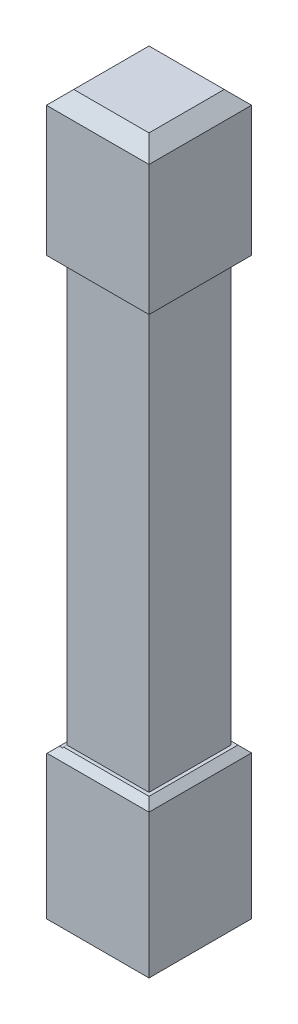
SolidWorks part; units mm, degrees
ref_plane "Plan de face" through (0, 0, 0) normal (0, 0, 1) x (1, 0, 0)
ref_plane "Plan de dessus" through (0, 0, 0) normal (0, 1, 0) x (1, 0, 0)
ref_plane "Plan de droite" through (0, 0, 0) normal (1, 0, 0) x (0, 0, -1)
sketch "Esquisse1" plane through (0, 0, 0) normal (0, 0, 1) x (1, 0, 0)
  line L0 (0, 658.8921) -> (0, -474.8551) construction
  line L2 (0, 685.5097) -> (-75, 685.5097)
  line L3 (0, 685.5097) -> (0, -364.4903)
  line L4 (0, -364.4903) -> (-75, -364.4903)
  line L5 (-75, 685.5097) -> (-75, -364.4903)
  dimension "D1" = 1050
  dimension "D2" = 75
extrude "Boss.-Extru.2" add sketch "Esquisse1" along normal blind 150
mirror "Symétrie1" about plane through (0, 685.5097, 150) normal (-1, 0, 0) of "Boss.-Extru.2"
sketch "Esquisse2" plane through (0, 0, 0) normal (0, 0, 1) x (1, 0, 0)
  line L0 (75, 685.5097) -> (-75, 685.5097) construction
  line L1 (-113.4667, 465.5097) -> (113.4667, 465.5097)
  line L2 (-113.4667, 465.5097) -> (-113.4667, -144.4903)
  line L3 (-113.4667, -144.4903) -> (113.4667, -144.4903)
  line L4 (113.4667, 465.5097) -> (113.4667, -144.4903)
  dimension "D1" = 610
  dimension "D2" = 220
extrude "Enlèv. mat.-Extru.1" cut sketch "Esquisse2" along normal blind 15
sketch "Esquisse3" plane through (-75, 0, 0) normal (-1, 0, 0) x (0, 0, 1)
  line L1 (0, 465.5097) -> (179.7824, 465.5097)
  line L2 (0, 465.5097) -> (0, -145.4548)
  line L3 (0, -145.4548) -> (179.7824, -145.4548)
  line L4 (179.7824, 465.5097) -> (179.7824, -145.4548)
extrude "Enlèv. mat.-Extru.2" cut sketch "Esquisse3" against normal blind 15
sketch "Esquisse4" plane through (75, 0, 0) normal (1, 0, 0) x (0, 0, -1)
  line L1 (0, 465.5097) -> (-199.3417, 465.5097)
  line L2 (0, 465.5097) -> (0, -144.4903)
  line L3 (0, -144.4903) -> (-199.3417, -144.4903)
  line L4 (-199.3417, 465.5097) -> (-199.3417, -144.4903)
extrude "Enlèv. mat.-Extru.3" cut sketch "Esquisse4" against normal blind 15
sketch "Esquisse5" plane through (0, 0, 150) normal (0, 0, 1) x (1, 0, 0)
  line L1 (-75, 465.5097) -> (75, 465.5097)
  line L2 (-75, 465.5097) -> (-75, -144.4903)
  line L3 (-75, -144.4903) -> (75, -144.4903)
  line L4 (75, 465.5097) -> (75, -144.4903)
extrude "Enlèv. mat.-Extru.4" cut sketch "Esquisse5" against normal blind 15
chamfer "Chanfrein1" distance 20 angle 45 4 edges at (-75, 685.5097, 75) (0, 685.5097, 0) (75, 685.5097, 75) (0, 685.5097, 150)
chamfer "Chanfrein2" distance 10 angle 45 4 edges at (0, 465.5097, 150) (-75, 465.5097, 75) (0, 465.5097, 0) (75, 465.5097, 75)
chamfer "Chanfrein3" distance 10 angle 45 4 edges at (-75, -145.4548, 75) (7.5, -144.4903, 150) (7.5, -144.4903, 0) (75, -144.4903, 75)
